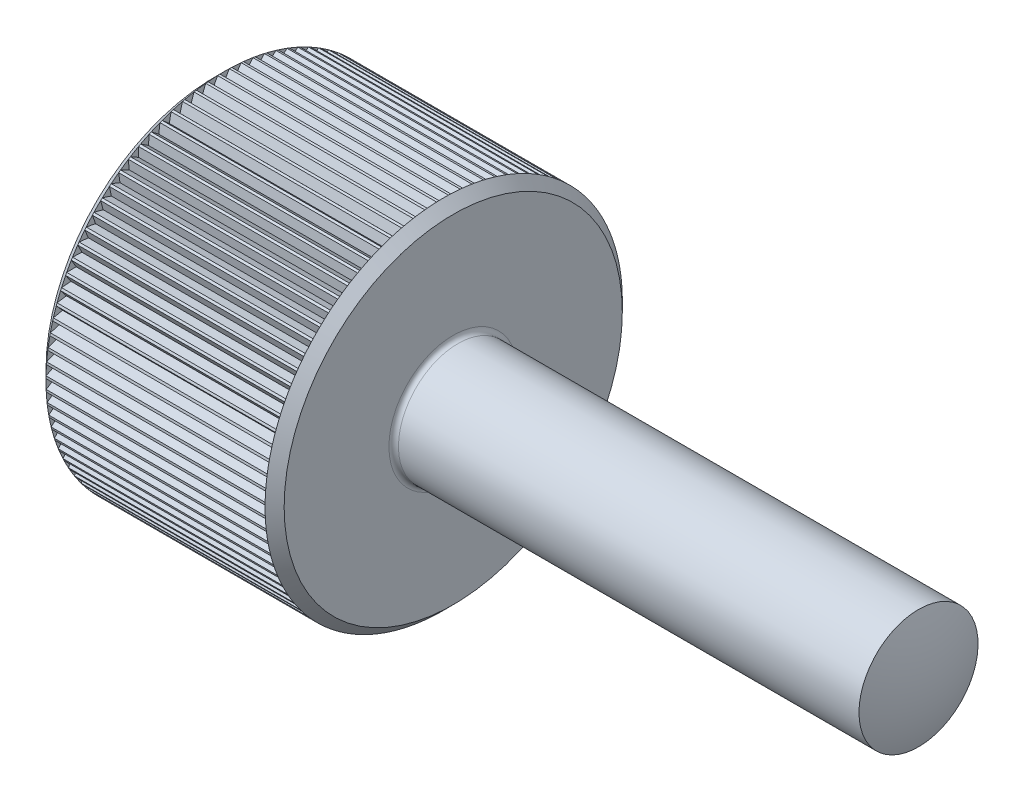
SolidWorks part; units mm, degrees
ref_plane "Front" through (0, 0, 0) normal (0, 0, 1) x (1, 0, 0)
ref_plane "Top" through (0, 0, 0) normal (0, 1, 0) x (1, 0, 0)
ref_plane "Right" through (0, 0, 0) normal (1, 0, 0) x (0, 0, -1)
sketch "Sketch1" plane through (0, 0, 0) normal (0, 0, 1) x (1, 0, 0)
  line L0 (0, 0) -> (0, 15)
  line L1 (0, 15) -> (20, 15)
  line L2 (20, 15) -> (20, 5)
  line L7 (20, 5) -> (59.0767, 5)
  line L8 (0, 0) -> (60, 0)
  line L9 (-48.2111, 0) -> (101.1311, 0) construction
  arc A0 (60, 0) -> (59.0767, 5) centre (46, 0) ccw
  dimension "l" = 40
  dimension "d" = 10
revolve "Base" add sketch "Sketch1" angle 360 about L9
cosmetic thread "ThreadCosmetic1" [suppressed] parameters "D1"=40, "THD_MINOR"=8
chamfer "Chamfer1" distance 0.8 angle 45 2 edges at (0, 0, 15) (20, 0, 15)
ref_plane "Plane1" through (19.2, 0, 0) normal (1, 0, 0) x (0, 0, -1)
sketch "Sketch3" plane through (19.2, 0, 0) normal (1, 0, 0) x (0, 0, -1)
  line L1 (0, 14.3072) -> (0.6, 15.3464)
  line L2 (0.6, 15.3464) -> (-0.6, 15.3464)
  line L3 (-0.6, 15.3464) -> (0, 14.3072)
  circle A1 centre (0, 0) radius 15 construction
  circle A2 centre (0, 15) radius 0.3464 construction
  dimension "D1" = 1.2
extrude "Cut-Extrude1" cut sketch "Sketch3" against normal blind 18.4
pattern_circular "Circular-Pattern1" count 95 over 360 about axis through (-48.2111, 0, 0) along (1, 0, 0) of "Cut-Extrude1"
fillet "Fillet1" radius 0.4 1 edges at (20, 0, 5)
sketch "Sketch4" plane through (0, 0, 0) normal (0, 0, 1) x (1, 0, 0)
  line L0 (20.4, 6) -> (21.4, 6)
  line L1 (21.4, 6) -> (21.4, 5)
  line L2 (21.4, 5) -> (20.9, 4.134)
  line L3 (20.9, 4.134) -> (20.4, 5)
  line L4 (20.4, 5) -> (20.4, 6)
  line L5 (20.4, -5) -> (20.4, 5) construction
  line L6 (59.0767, 5) -> (20.4, 5) construction
  dimension "D1" = 1
revolve "Cut-Revolve10" [suppressed] cut sketch "Sketch4" angle 360 about axis through (-48.2111, 0, 0) along (1, 0, 0)
pattern_linear "LPattern10" [suppressed] count 33 along (1, 0, 0) of bodies 104
equation "\"D1@Circular-Pattern1\" =int (  \"dk@Sketch1\" * PI+1 ) "
equation "\"D1@ThreadCosmetic1\" = \"l@Sketch1\""
equation "\"D1@Plane1\" = \"c@Chamfer1\""
equation "\"D1@Cut-Extrude1\" = \"k@Sketch1\" - 2 * \"c@Chamfer1\""
equation "\"D1@Sketch4\" =  ( \"d@Sketch1\" - \"THD_MINOR@ThreadCosmetic1\" )  / 2"
equation "\"pitch@LPattern10\" = 1.2 * \"D1@Sketch4\""
equation "\"D1@LPattern10\" = (  \"D1@ThreadCosmetic1\" - \"r@Fillet1\" )  / \"pitch@LPattern10\""
equation "\"D1@Sketch3\" = \"c@Chamfer1\" * 1.5"
